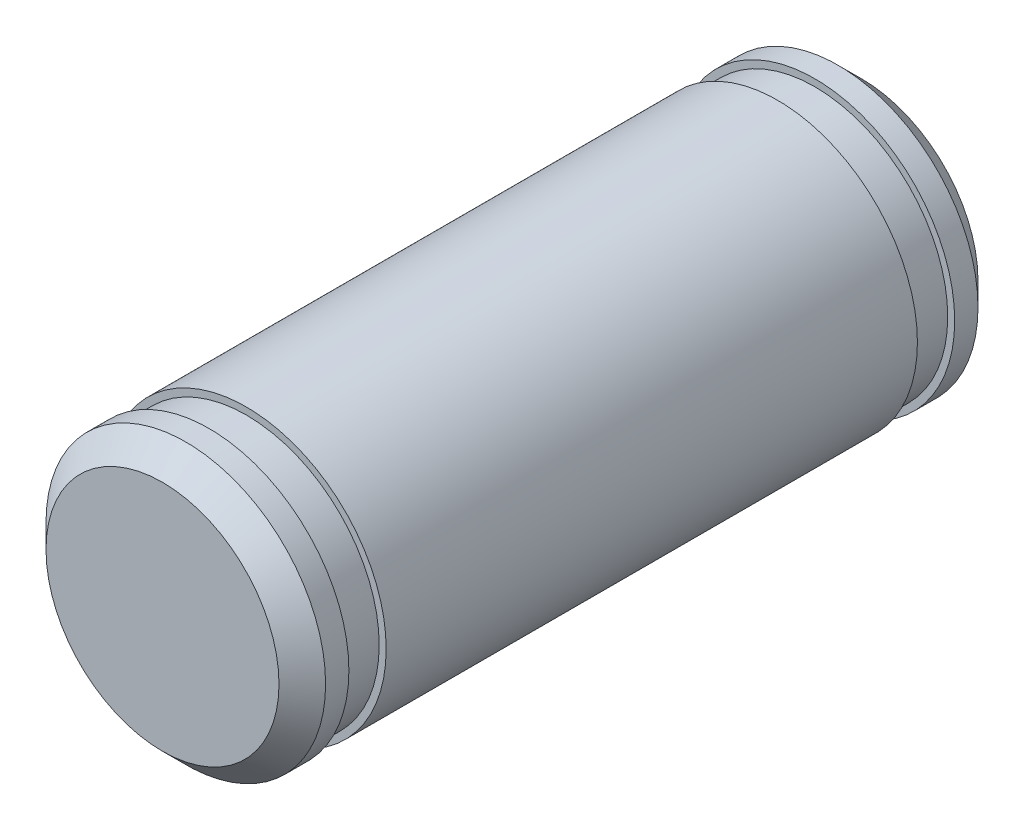
SolidWorks part; units mm, degrees
material "Stop 1060"
ref_plane "Płaszczyzna przednia" through (0, 0, 0) normal (0, 0, 1) x (1, 0, 0)
ref_plane "Płaszczyzna górna" through (0, 0, 0) normal (0, 1, 0) x (1, 0, 0)
ref_plane "Płaszczyzna prawa" through (0, 0, 0) normal (1, 0, 0) x (0, 0, -1)
sketch "Szkic1" plane through (0, 0, 0) normal (0, 0, 1) x (1, 0, 0)
  circle A0 centre (0, 0) radius 3
  dimension "D1" = 6
extrude "Dodanie-wyciągnięcie1" add sketch "Szkic1" along normal blind 15
chamfer "Sfazowanie1" distance 0.5 angle 45 2 edges at (3, 0, 0) (3, 0, 15)
sketch "Szkic2" plane through (0, 0, 15) normal (0, 0, 1) x (1, 0, 0)
  circle A0 centre (0, 0) radius 3
  circle A1 centre (0, 0) radius 2.85
  dimension "D1" = 6
  dimension "D2" = 5.7
extrude "Wytnij-wyciągnięcie1" cut sketch "Szkic2" against normal blind 0.8 from offset 1 offset against normal yes
sketch "Szkic3" plane through (0, 0, 0) normal (0, 0, -1) x (-1, 0, 0)
  circle A0 centre (0, 0) radius 3
  circle A1 centre (0, 0) radius 2.85
  dimension "D1" = 5.7
  dimension "D2" = 6
extrude "Wytnij-wyciągnięcie2" cut sketch "Szkic3" against normal blind 0.8 from offset 1 offset against normal yes
